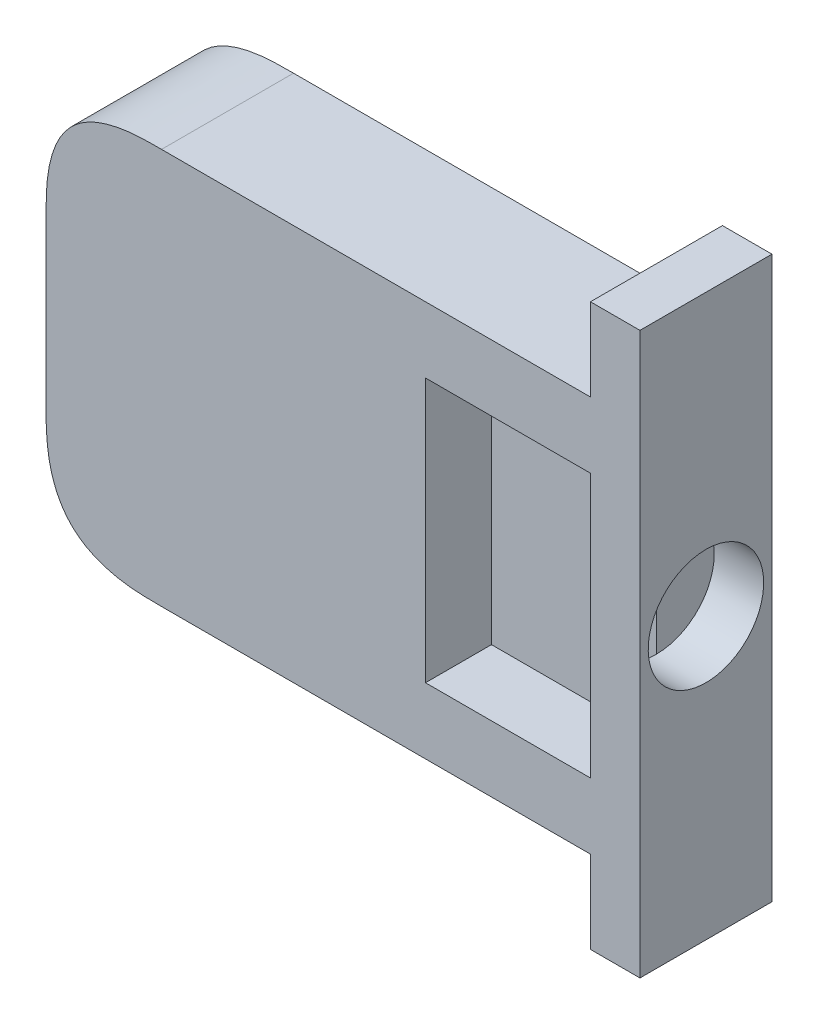
SolidWorks part; units mm, degrees
ref_plane "Front Plane" through (0, 0, 0) normal (0, 0, 1) x (1, 0, 0)
ref_plane "Top Plane" through (0, 0, 0) normal (0, 1, 0) x (1, 0, 0)
ref_plane "Right Plane" through (0, 0, 0) normal (1, 0, 0) x (0, 0, -1)
sketch "Sketch1" plane through (0, 0, 0) normal (0, 0, 1) x (1, 0, 0)
  line L0 (-6, -12) -> (-6, 12)
  line L1 (-6, 12) -> (27, 12)
  line L2 (27, 12) -> (27, 17)
  line L3 (27, 17) -> (30, 17)
  line L4 (30, 17) -> (30, -17)
  line L6 (27, -17) -> (30, -17)
  line L7 (27, -12) -> (27, -17)
  line L8 (-6, -12) -> (27, -12)
  line L9 (0, 0) -> (30, 0)
  dimension "D1" = 3
  dimension "D2" = 3
  dimension "D3" = 33
  dimension "D4" = 5
  dimension "D5" = 34
  dimension "D6" = 12
  dimension "D7" = 24
  dimension "D8" = 33
extrude "Boss-Extrude1" add sketch "Sketch1" along normal blind 8 contours L4 L6 L7 L8 L0 L1 L2 L3
fillet "Fillet3" radius 7 2 edges at (-6, 12, 4) (-6, -12, 4) curvature continuous yes
ref_plane "Plane1" through (0, 0, 8) normal (0, 0, 1) x (1, 0, 0)
sketch "Sketch2" plane through (0, 0, 8) normal (0, 0, 1) x (1, 0, 0)
  line L0 (17, 0) -> (27, 0)
  line L1 (1, -12) -> (27, -12) construction
  line L2 (17, -8) -> (17, 8)
  line L3 (17, 8) -> (27, 8)
  line L4 (30, 17) -> (30, -17) construction
  line L5 (27, 8) -> (27, -8)
  line L6 (17, 0) -> (27, 0)
  line L7 (17, -8) -> (27, -8)
  line L8 (1, 12) -> (27, 12) construction
  line L9 (27, 12) -> (27, 17) construction
  line L10 (27, -12) -> (27, -17) construction
  dimension "D1" = 8
  dimension "D2" = 3
  dimension "D3" = 10
  dimension "D4" = 4
  dimension "D5" = 4
extrude "Cut-Extrude1" cut sketch "Sketch2" against normal blind 4 contours L5 L3 L2 L0 | L2 L7 L5 L0 region at (22, 4, 8) region at (22, -4, 8)
ref_plane "Plane2" through (30, 0, 0) normal (1, 0, 0) x (0, 0, -1)
sketch "Sketch3" plane through (30, 0, 0) normal (1, 0, 0) x (0, 0, -1)
  circle A0 centre (-4, 0) radius 3.5
extrude "Cut-Extrude2" cut sketch "Sketch3" against normal blind 3
